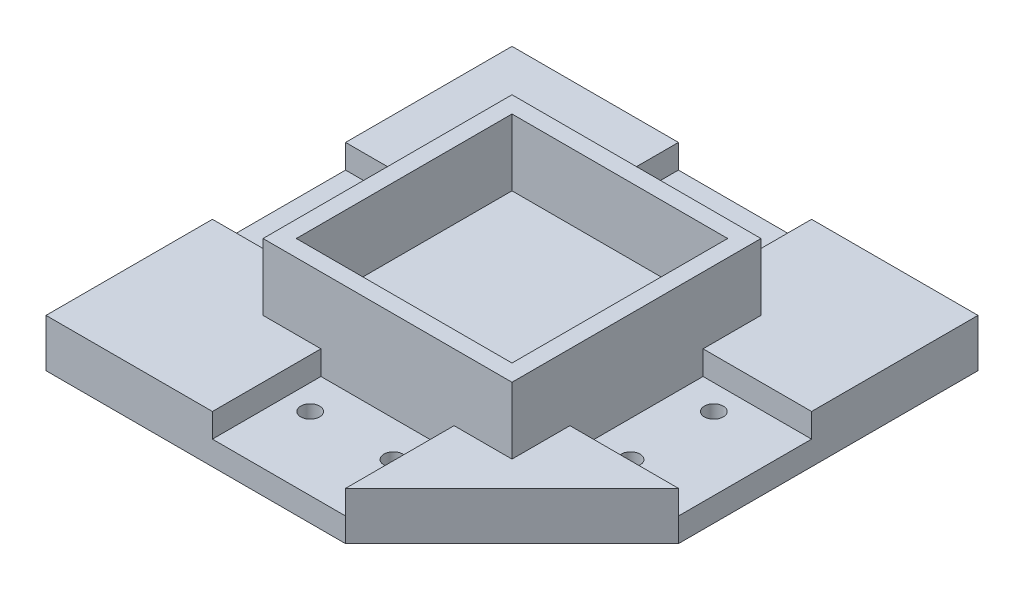
SolidWorks part; units mm, degrees
material "6061 Alloy"
ref_plane "Front Plane" through (0, 0, 0) normal (0, 0, 1) x (1, 0, 0)
ref_plane "Top Plane" through (0, 0, 0) normal (0, 1, 0) x (1, 0, 0)
ref_plane "Right Plane" through (0, 0, 0) normal (1, 0, 0) x (0, 0, -1)
sketch "Sketch1" plane through (0, 0, 0) normal (0, 1, 0) x (1, 0, 0)
  line L1 (0, 0) -> (88.9, 0)
  line L2 (0, 0) -> (0, 88.9)
  line L3 (0, 88.9) -> (88.9, 88.9)
  line L4 (88.9, 0) -> (88.9, 88.9)
  dimension "D1" = 88.9
  dimension "D2" = 88.9
extrude "Boss-Extrude1" add sketch "Sketch1" along normal blind 9.144
sketch "Sketch2" plane through (0, 9.144, 0) normal (0, 1, 0) x (1, 0, 0)
  line L0 (88.9, 88.9) -> (0, 88.9) construction
  line L1 (31.75, 88.9) -> (57.15, 88.9)
  line L2 (31.75, 88.9) -> (31.75, 67.31)
  line L3 (31.75, 67.31) -> (57.15, 67.31)
  line L4 (57.15, 88.9) -> (57.15, 67.31)
  line L5 (0, 88.9) -> (0, 0) construction
  line L6 (0, 57.15) -> (21.59, 57.15)
  line L7 (0, 57.15) -> (0, 31.75)
  line L8 (0, 31.75) -> (21.59, 31.75)
  line L9 (21.59, 57.15) -> (21.59, 31.75)
  line L10 (0, 0) -> (88.9, 0) construction
  line L11 (31.75, 0) -> (57.15, 0)
  line L12 (31.75, 0) -> (31.75, 21.59)
  line L13 (31.75, 21.59) -> (57.15, 21.59)
  line L14 (57.15, 0) -> (57.15, 21.59)
  line L15 (88.9, 0) -> (88.9, 88.9) construction
  line L16 (88.9, 57.15) -> (67.31, 57.15)
  line L17 (88.9, 57.15) -> (88.9, 31.75)
  line L18 (88.9, 31.75) -> (67.31, 31.75)
  line L19 (67.31, 57.15) -> (67.31, 31.75)
  dimension "D1" = 31.75
  dimension "D2" = 25.4
  dimension "D3" = 25.4
  dimension "D4" = 31.75
  dimension "D5" = 25.4
  dimension "D6" = 31.75
  dimension "D7" = 25.4
  dimension "D8" = 31.75
  dimension "D9" = 21.59
  dimension "D10" = 21.59
  dimension "D11" = 21.59
  dimension "D12" = 21.59
extrude "Cut-Extrude1" cut sketch "Sketch2" against normal blind 4.572
sketch "Sketch3" plane through (0, 9.144, 0) normal (0, 1, 0) x (1, 0, 0)
  line L0 (31.75, 88.9) -> (0, 88.9) construction
  line L1 (20.6375, 68.2625) -> (68.2625, 68.2625)
  line L2 (20.6375, 68.2625) -> (20.6375, 20.6375)
  line L3 (20.6375, 20.6375) -> (68.2625, 20.6375)
  line L4 (68.2625, 68.2625) -> (68.2625, 20.6375)
  line L5 (0, 31.75) -> (0, 0) construction
  line L6 (88.9, 31.75) -> (88.9, 57.15) construction
  line L7 (57.15, 88.9) -> (31.75, 88.9) construction
  line L8 (0, 57.15) -> (0, 31.75) construction
  line L9 (31.75, 0) -> (57.15, 0) construction
  circle A0 centre (28.194, 44.45) radius 2.4
  circle A1 centre (44.45, 60.706) radius 2.4
  circle A2 centre (60.706, 44.45) radius 2.4
  circle A3 centre (44.45, 28.194) radius 2.4
  dimension "D5" = 4.8
  dimension "D6" = 4.8
  dimension "D7" = 4.8
  dimension "D8" = 4.8
  dimension "D1" = 47.625
  dimension "D2" = 47.625
  dimension "D3" = 20.6375
  dimension "D4" = 20.6375
  dimension "D9" = 28.194
  dimension "D10" = 28.194
  dimension "D11" = 28.194
  dimension "D12" = 28.194
  dimension "D13" = 23.8125
  dimension "D14" = 23.8125
  dimension "D15" = 23.8125
  dimension "D16" = 23.8125
extrude "Cut-Extrude2" [suppressed] cut sketch "Sketch3" against normal through all contours A2 | A1 | A0 | A3
sketch "Sketch4" plane through (0, 4.572, 0) normal (0, 1, 0) x (1, 0, 0)
  line L0 (0, 57.15) -> (0, 31.75) construction
  line L1 (57.15, 88.9) -> (31.75, 88.9) construction
  line L2 (88.9, 31.75) -> (88.9, 57.15) construction
  line L3 (31.75, 0) -> (57.15, 0) construction
  line L4 (0, 31.75) -> (21.59, 31.75) construction
  line L5 (31.75, 21.59) -> (31.75, 0) construction
  line L6 (67.31, 31.75) -> (88.9, 31.75) construction
  line L7 (57.15, 67.31) -> (57.15, 88.9) construction
  circle A0 centre (75.0062, 52.3875) radius 1.8034
  circle A1 centre (75.0062, 36.5125) radius 1.8034
  circle A2 centre (52.3875, 75.0062) radius 1.8034
  circle A3 centre (36.5125, 75.0062) radius 1.8034
  circle A4 centre (13.8938, 52.3875) radius 1.8034
  circle A5 centre (13.8938, 36.5125) radius 1.8034
  circle A6 centre (36.5125, 13.8938) radius 1.8034
  circle A7 centre (52.3875, 13.8938) radius 1.8034
  dimension "D1" = 3.6068
  dimension "D2" = 3.6068
  dimension "D3" = 3.6068
  dimension "D4" = 3.6068
  dimension "D5" = 3.6068
  dimension "D6" = 3.6068
  dimension "D7" = 3.6068
  dimension "D8" = 3.6068
  dimension "D9" = 13.8938
  dimension "D10" = 13.8938
  dimension "D11" = 13.8938
  dimension "D12" = 13.8938
  dimension "D13" = 13.8938
  dimension "D14" = 13.8938
  dimension "D15" = 13.8938
  dimension "D16" = 13.8938
  dimension "D17" = 15.875
  dimension "D18" = 4.7625
  dimension "D19" = 4.7625
  dimension "D20" = 15.875
  dimension "D21" = 4.7625
  dimension "D22" = 15.875
  dimension "D23" = 4.7625
  dimension "D24" = 15.875
extrude "Cut-Extrude3" cut sketch "Sketch4" against normal through all
sketch "Sketch5" plane through (0, 9.144, 0) normal (0, 1, 0) x (1, 0, 0)
  line L0 (88.9, 88.9) -> (57.15, 88.9) construction
  line L1 (88.9, 31.75) -> (88.9, 57.15) construction
  circle A0 centre (44.45, 44.45) radius 6.35
  dimension "D1" = 12.7
  dimension "D2" = 44.45
  dimension "D3" = 44.45
extrude "Cut-Extrude4" [suppressed] cut sketch "Sketch5" against normal through all
sketch "Sketch6" plane through (0, 9.144, 0) normal (0, 1, 0) x (1, 0, 0)
  line L0 (88.9, 31.75) -> (57.15, 0)
  line L1 (57.15, 0) -> (88.9, 0)
  line L2 (88.9, 0) -> (88.9, 31.75)
extrude "Cut-Extrude5" cut sketch "Sketch6" against normal through all
sketch "Sketch7" plane through (0, 9.144, 0) normal (0, 1, 0) x (1, 0, 0)
  line L0 (0, 88.9) -> (0, 57.15) construction
  line L1 (20.701, 68.199) -> (68.199, 68.199)
  line L2 (20.701, 68.199) -> (20.701, 20.701)
  line L3 (20.701, 20.701) -> (68.199, 20.701)
  line L4 (68.199, 68.199) -> (68.199, 20.701)
  line L5 (0, 0) -> (31.75, 0) construction
  line L7 (23.876, 23.876) -> (65.024, 23.876)
  line L8 (23.876, 23.876) -> (23.876, 65.024)
  line L9 (23.876, 65.024) -> (65.024, 65.024)
  line L10 (65.024, 23.876) -> (65.024, 65.024)
  dimension "D1" = 47.498
  dimension "D2" = 47.498
  dimension "D3" = 20.701
  dimension "D4" = 20.701
  dimension "D5" = 3.175
  dimension "D6" = 3.175
  dimension "D7" = 3.175
  dimension "D8" = 3.175
extrude "Boss-Extrude2" add sketch "Sketch7" along normal blind 12.7 and the other way up to next (4.572 mm away)
equation "\"hinge_hole\"= 0.142in"
equation "\"D1@Sketch4\"=\"hinge_hole\""
equation "\"D2@Sketch4\"=\"hinge_hole\""
equation "\"D3@Sketch4\"=\"hinge_hole\""
equation "\"D4@Sketch4\"=\"hinge_hole\""
equation "\"D5@Sketch4\"=\"hinge_hole\""
equation "\"D6@Sketch4\"=\"hinge_hole\""
equation "\"D7@Sketch4\"=\"hinge_hole\""
equation "\"D8@Sketch4\"=\"hinge_hole\""
equation "\"hinge_hole_dist\"= 0.297 + 0.25"
equation "\"D9@Sketch4\"=\"hinge_hole_dist\""
equation "\"D10@Sketch4\"=\"hinge_hole_dist\""
equation "\"D11@Sketch4\"=\"hinge_hole_dist\""
equation "\"D12@Sketch4\"=\"hinge_hole_dist\""
equation "\"D13@Sketch4\"=\"hinge_hole_dist\""
equation "\"D14@Sketch4\"=\"hinge_hole_dist\""
equation "\"D15@Sketch4\"=\"hinge_hole_dist\""
equation "\"D16@Sketch4\"=\"hinge_hole_dist\""
equation "\"hinge_hole_sep\"= 0.625"
equation "\"hinge_hole_from_wall\"= ( 1 - \"hinge_hole_sep\" ) / 2"
equation "\"D17@Sketch4\"=\"hinge_hole_sep\""
equation "\"D18@Sketch4\"=\"hinge_hole_from_wall\""
equation "\"D19@Sketch4\"=\"hinge_hole_from_wall\""
equation "\"D20@Sketch4\"=\"hinge_hole_sep\""
equation "\"D21@Sketch4\"=\"hinge_hole_from_wall\""
equation "\"D22@Sketch4\"=\"hinge_hole_sep\""
equation "\"D23@Sketch4\"=\"hinge_hole_from_wall\""
equation "\"D24@Sketch4\"=\"hinge_hole_sep\""
equation "\"D9@Sketch2\"=\"hinge_hole_dist\" + (0.6-0.297)"
equation "\"D12@Sketch2\"=\"hinge_hole_dist\" + (0.6-0.297)"
equation "\"D11@Sketch2\"=\"hinge_hole_dist\" + (0.6-0.297)"
equation "\"D10@Sketch2\"=\"hinge_hole_dist\" + (0.6-0.297)"
